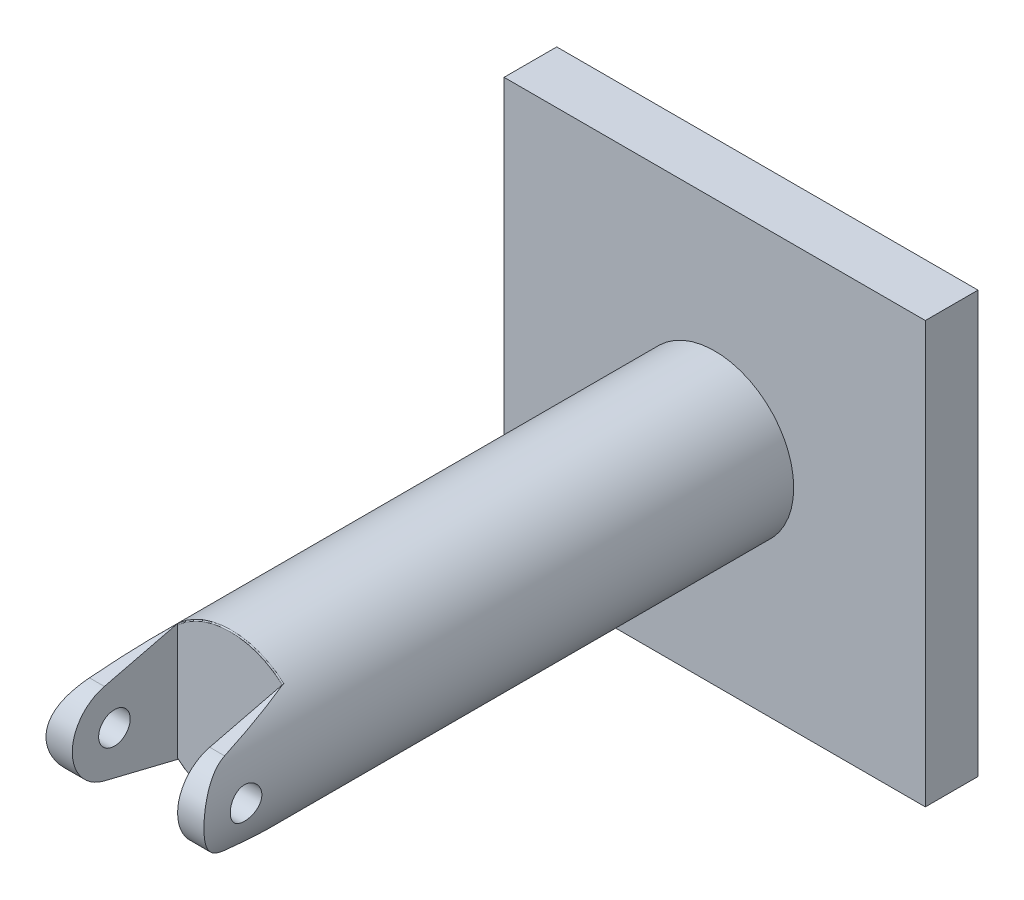
SolidWorks part; units mm, degrees
material "Alloy Steel"
ref_plane "Ön Düzlem" through (0, 0, 0) normal (0, 0, 1) x (1, 0, 0)
ref_plane "Üst Düzlem" through (0, 0, 0) normal (0, 1, 0) x (1, 0, 0)
ref_plane "Sağ Düzlem" through (0, 0, 0) normal (1, 0, 0) x (0, 0, -1)
sketch "Sketch1" plane through (0, 0, 0) normal (0, 0, 1) x (1, 0, 0)
  circle A0 centre (0, 0) radius 7.5
  dimension "D1" = 15
extrude "Boss-Extrude1" add sketch "Sketch1" along normal blind 56
sketch "Sketch2" plane through (0, 0, 56) normal (0, 0, 1) x (1, 0, 0)
  line L1 (-5, 8) -> (5, 8)
  line L2 (-5, 8) -> (-5, -8)
  line L3 (-5, -8) -> (5, -8)
  line L4 (5, 8) -> (5, -8)
  dimension "D1" = 10
  dimension "D2" = 5
  dimension "D3" = 8
  dimension "D4" = 8
extrude "Cut-Extrude1" cut sketch "Sketch2" along direction (0, 0, 1) on the side against the normal blind 10
sketch "Sketch3" plane through (0, 0, 0) normal (1, 0, 0) x (0, 0, -1)
  line L0 (-46, -7.5) -> (-46, -5.5902)
  line L1 (-46, 7.5) -> (-46, 5.5902)
  line L2 (-46, 5.5902) -> (-52.9529, 3.8847)
  line L3 (-46, -5.5902) -> (-52.9527, -3.885)
  line L4 (-56, -5.5902) -> (-46, -5.5902) construction
  line L5 (-56, 5.5902) -> (-56, -5.5902) construction
  arc A0 (-52.9529, 3.8847) -> (-52.9527, -3.885) centre (-52, -0.0002) ccw
  dimension "D1" = 4
  dimension "D2" = 5.59
extrude "Cut-Extrude4" cut sketch "Sketch3" against normal through all and the other way through all flip side to cut
sketch "Sketch4" plane through (0, 0, 0) normal (1, 0, 0) x (0, 0, -1)
  circle A0 centre (-52, -0.0002) radius 1.5
  arc A1 (-52.9529, 3.8847) -> (-52.9527, -3.885) centre (-52, -0.0002) ccw construction
  dimension "D1" = 3
extrude "Cut-Extrude5" cut sketch "Sketch4" against normal through all and the other way through all
fillet "Fillet1" radius 0.1 2 edges at (0, 7.5, 46) (0, -7.5, 46)
sketch "Sketch5" plane through (0, 0, 0) normal (0, 0, -1) x (-1, 0, 0)
  line L1 (-20, -20) -> (20, -20)
  line L2 (-20, -20) -> (-20, 20)
  line L3 (-20, 20) -> (20, 20)
  line L4 (20, -20) -> (20, 20)
  line L5 (-20, -20) -> (20, 20) construction
  line L6 (-20, 20) -> (20, -20) construction
  point P0 (0, 0)
  dimension "D1" = 40
  dimension "D2" = 40
extrude "Boss-Extrude2" add sketch "Sketch5" along normal blind 5
